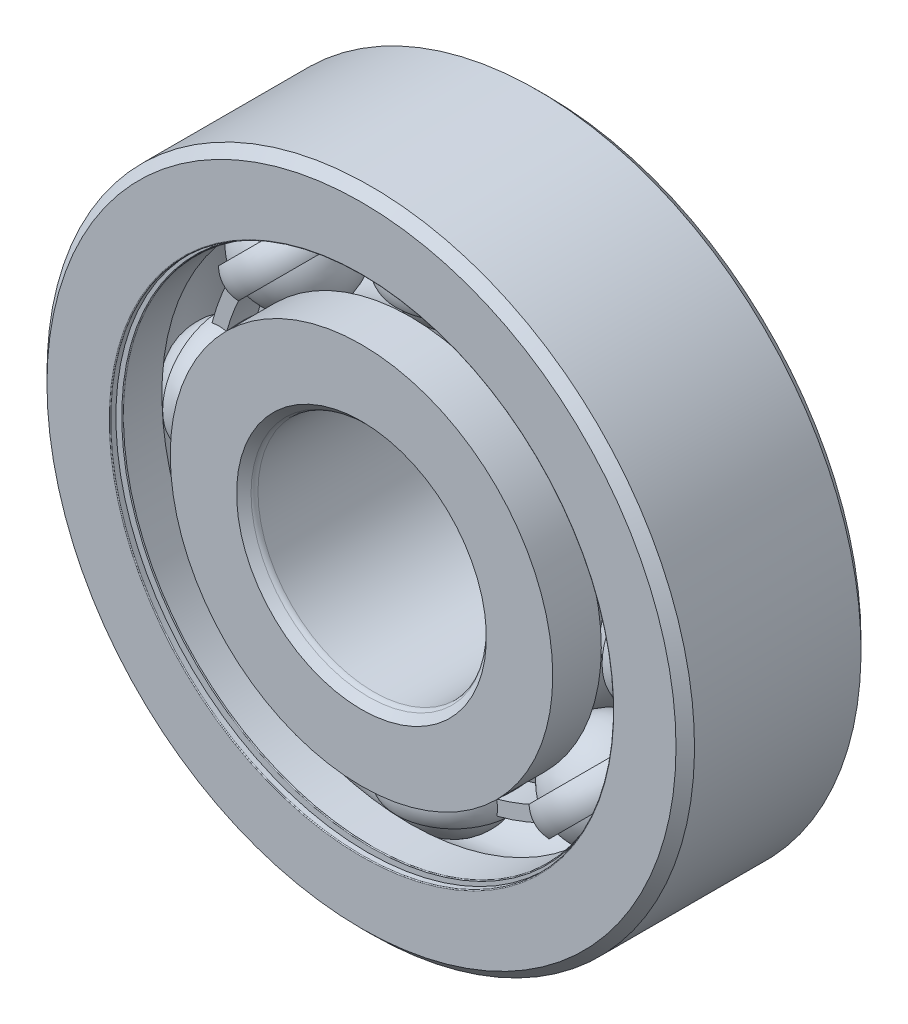
SolidWorks part; units mm, degrees
ref_plane "Front Plane" through (0, 0, 0) normal (0, 0, 1) x (1, 0, 0)
ref_plane "Top Plane" through (0, 0, 0) normal (0, 1, 0) x (1, 0, 0)
ref_plane "Right Plane" through (0, 0, 0) normal (1, 0, 0) x (0, 0, -1)
sketch "Sketch1" plane through (0, 0, 0) normal (0, 0, 1) x (1, 0, 0)
  line L0 (-14, 0) -> (14, 0) construction
  line L1 (-5, 0) -> (5, 0) construction
  circle A0 centre (0, 0) radius 5 construction
  circle A1 centre (0, 0) radius 14 construction
  point P3 (0, 0)
  point P6 (0, 0)
  point P7 (0, -5)
  point P11 (0, -14)
  point P12 (0, 5)
  point P13 (0, 14)
  dimension "OD" = 28
  dimension "ID" = 10
sketch "Sketch2" plane through (0, 0, 0) normal (1, 0, 0) x (0, 0, -1)
  line L0 (-4, 14) -> (4, 14) construction
  line L1 (0, 14) -> (0, -14) construction
  line L2 (3.6, 14) -> (-3.6, 14)
  line L3 (-3.6, 14) -> (-4, 13.6)
  line L4 (-4, 13.6) -> (-4, 10.7308)
  line L5 (-4, 10.7308) -> (-1.9, 10.7308)
  line L6 (4, 10.7308) -> (1.9, 10.7308)
  line L7 (4, 13.6) -> (4, 10.7308)
  line L8 (3.6, 14) -> (4, 13.6)
  line L9 (0, 14) -> (0, 9.5) construction
  line L10 (0, 9.5) -> (0, 5) construction
  line L11 (0, 14) -> (0, -14) construction
  line L12 (-4, 0) -> (4, 0) construction
  line L13 (4, 5) -> (-4, 5) construction
  line L14 (0, 11.7638) -> (0, 7.2362) construction
  line L15 (-4, -5) -> (4, -5) construction
  line L16 (-4, -5) -> (-4, 5) construction
  line L17 (4, 14) -> (4, -14) construction
  arc A0 (-1.9, 10.7308) -> (1.9, 10.7308) centre (0, 9.5) cw
  circle A1 centre (0, 9.5) radius 2.2638 construction
  point P14 (0, 5)
  point P17 (0, 0)
  point P21 (0, 14)
  point P29 (0, 5)
  point P30 (0, -5)
  point P35 (0, 11.7638)
  dimension "Approx. Ball Dia." = 4.5276
  dimension "Width" = 8
  dimension "D1" = 45
  dimension "D2" = 0.4
  dimension "D3" = 3.8
  dimension "D4" = 1.2308
  dimension "For Shaft Diameter" = 10
  dimension "For Housing ID" = 28
sketch "Sketch3" plane through (0, 0, 0) normal (1, 0, 0) x (0, 0, -1)
  line L0 (3.6, 14) -> (4, 13.6) construction
  line L1 (4, 13.6) -> (4, 10.7308) construction
  line L2 (4, 10.7308) -> (1.9, 10.7308) construction
  line L3 (-4, 10.7308) -> (-1.9, 10.7308) construction
  line L4 (-4, 13.6) -> (-4, 10.7308) construction
  line L5 (-3.6, 14) -> (-4, 13.6) construction
  line L6 (3.6, 14) -> (-3.6, 14) construction
  line L7 (3.6, 14) -> (4, 13.6)
  line L8 (4, 13.6) -> (4, 10.7308)
  line L9 (4, 10.7308) -> (1.9, 10.7308)
  line L10 (-4, 10.7308) -> (-1.9, 10.7308)
  line L11 (-4, 13.6) -> (-4, 10.7308)
  line L12 (-3.6, 14) -> (-4, 13.6)
  line L13 (3.6, 14) -> (-3.6, 14)
  arc A0 (1.9, 10.7308) -> (-1.9, 10.7308) centre (0, 9.5) ccw construction
  arc A1 (1.9, 10.7308) -> (-1.9, 10.7308) centre (0, 9.5) ccw
revolve "Revolve1" add sketch "Sketch3" angle 360 about L12
sketch "Sketch8" plane through (0, 0, 0) normal (1, 0, 0) x (0, 0, -1)
  line L0 (-4, 10.7308) -> (-1.9, 10.7308) construction
  line L1 (-3.744, 10.7308) -> (-3.6, 10.7308)
  line L2 (-3.744, 10.7308) -> (-3.744, 11.8205) construction
  line L3 (-3.744, 11.8205) -> (-3.6, 11.8205)
  line L4 (-3.6, 10.7308) -> (-3.6, 11.8205)
  line L5 (4, 10.7308) -> (1.9, 10.7308) construction
  line L6 (3.6, 10.7308) -> (3.744, 10.7308)
  line L7 (3.6, 10.7308) -> (3.6, 11.8205)
  line L8 (3.6, 11.8205) -> (3.744, 11.8205)
  line L9 (3.744, 10.7308) -> (3.744, 11.8205) construction
  line L10 (-3.6, 11.8205) -> (3.6, 11.8205) construction
  line L11 (0, 14) -> (0, -14) construction
  line L12 (-3.744, 11.8205) -> (-3.744, 12.9103) construction
  line L13 (-3.744, 12.9103) -> (-3.744, 14) construction
  line L14 (-4, 14) -> (4, 14) construction
  line L15 (-3.744, 10.7308) -> (-4, 10.7308)
  line L16 (-4, 10.7308) -> (-4, 10.8748)
  line L17 (-4, 13.6) -> (-4, 10.7308) construction
  line L18 (-4, 10.8748) -> (-3.744, 10.8748)
  line L19 (-3.744, 10.8748) -> (-3.744, 11.8205)
  line L20 (3.744, 10.7308) -> (4, 10.7308)
  line L21 (4, 10.7308) -> (4, 10.8748)
  line L22 (4, 13.6) -> (4, 10.7308) construction
  line L23 (4, 10.8748) -> (3.744, 10.8748)
  line L24 (3.744, 10.8748) -> (3.744, 11.8205)
  point P12 (0, 11.8205)
  dimension "D1" = 7.2
  dimension "D2" = 0.144
revolve "Cut-Revolve1" cut sketch "Sketch8" angle 360 about L12
sketch "Sketch4" plane through (0, 0, 0) normal (1, 0, 0) x (0, 0, -1)
  line L0 (0, 14) -> (0, -14) construction
  line L1 (0, 14) -> (0, -14) construction
  line L2 (-3.6, 5) -> (-4, 5.4)
  line L3 (-4, 5.4) -> (-4, 8.2692)
  line L5 (-4, 8.2692) -> (-1.9, 8.2692)
  line L6 (-3.6, 5) -> (3.6, 5)
  line L8 (3.6, 5) -> (4, 5.4)
  line L10 (4, 5.4) -> (4, 8.2692)
  line L11 (4, 8.2692) -> (1.9, 8.2692)
  line L12 (-4, 13.6) -> (-4, 10.7308) construction
  line L13 (3.6, 14) -> (4, 13.6) construction
  line L15 (4, -13.6) -> (4, 13.6) construction
  line L16 (3.6, 14) -> (3.6, -14) construction
  arc A1 (1.9, 8.2692) -> (-1.9, 8.2692) centre (0, 9.5) cw
  circle A2 centre (0, 9.5) radius 2.2638 construction
  point P1 (0, 5)
revolve "Revolve2" add sketch "Sketch4" angle 360 about L12
sketch "Sketch5" plane through (0, 0, 0) normal (1, 0, 0) x (0, 0, -1)
  line L0 (-2.2638, 9.5) -> (2.2638, 9.5)
  arc A2 (-2.2638, 9.5) -> (2.2638, 9.5) centre (0, 9.5) cw
  arc A3 (1.9, 10.7308) -> (-1.9, 10.7308) centre (0, 9.5) ccw construction
revolve "Revolve3" add sketch "Sketch5" angle 360 about L0
sketch "Sketch6" plane through (0, 0, 0) normal (1, 0, 0) x (0, 0, -1)
  line L0 (-1.9, 10.7308) -> (-1.9, 10.1154) construction
  line L1 (-1.9, 10.1154) -> (-1.9, 9.5) construction
  line L2 (-1.9, 9.5) -> (-1.9, 8.8846) construction
  line L3 (-1.9, 8.8846) -> (-1.9, 8.2692) construction
  line L4 (-4, 10.1154) -> (-3.6964, 10.1154) construction
  line L5 (-1.9, 10.1154) -> (-1.9, 8.8846) construction
  line L7 (-3.6964, 10.1154) -> (-3.3929, 10.1154) construction
  line L8 (-3.3929, 10.1154) -> (-3.0893, 10.1154) construction
  line L10 (0, 14) -> (0, -14) construction
  line L11 (0, 14) -> (0, -14) construction
  line L12 (-4, 10.7308) -> (-4, 10.1154) construction
  line L13 (-2.4821, 10.1154) -> (-2.1786, 10.1154) construction
  line L14 (-4, 13.6) -> (-4, -13.6) construction
  line L15 (-4, 10.1154) -> (-4, 9.5) construction
  line L16 (-4, 9.5) -> (-4, 8.8846) construction
  line L17 (-4, 8.8846) -> (-4, 8.2692) construction
  line L18 (-3.0893, 10.1154) -> (-2.7857, 10.1154) construction
  line L19 (-2.7857, 10.1154) -> (-2.4821, 10.1154) construction
  line L20 (-2.1786, 10.1154) -> (-2.4821, 10.1154)
  line L21 (-4, 8.8846) -> (-3.6964, 8.8846) construction
  line L22 (-3.6964, 8.8846) -> (-3.3929, 8.8846) construction
  line L23 (-3.3929, 8.8846) -> (-3.0893, 8.8846) construction
  line L24 (-3.0893, 8.8846) -> (-2.7857, 8.8846) construction
  line L25 (-2.7857, 8.8846) -> (-2.4821, 8.8846) construction
  line L26 (-2.4821, 8.8846) -> (-2.1786, 8.8846) construction
  line L27 (-2.1786, 8.8846) -> (-2.4821, 8.8846)
  line L28 (-2.7857, 10.1154) -> (-2.7857, 8.8846) construction
  line L30 (-2.6339, 10.1154) -> (-2.6339, 8.8846) construction
  circle A0 centre (0, 9.5) radius 2.2638 construction
  arc A2 (-2.4821, 8.8846) -> (-2.4821, 10.1154) centre (-1.3106, 9.5) cw
  arc A3 (-2.1786, 10.1154) -> (-2.1786, 8.8846) centre (0, 9.5) ccw
revolve "Revolve4" add sketch "Sketch6" angle 360 about L11
sketch "Sketch7" plane through (0, 0, 0) normal (0, 0, 1) x (1, 0, 0)
  line L0 (-2.2638, 9.5) -> (2.2638, 9.5) construction
  line L1 (0, 7.2362) -> (0, 11.7638) construction
  line L2 (0, 0) -> (3.6355, 8.7769) construction
  line L8 (0, 14) -> (0, -14) construction
  line L9 (6.7175, 6.7175) -> (7.1527, 7.1527)
  line L10 (0, 14) -> (0, -14) construction
  line L11 (0, 10.1154) -> (0, 9.5)
  arc A1 (6.7175, 6.7175) -> (0, 9.5) centre (0, 0) ccw
  arc A2 (7.1527, 7.1527) -> (0, 10.1154) centre (0, 0) ccw
  dimension "D1" = 45
  dimension "D2" = 4.5276
extrude "Boss-Extrude1" add sketch "Sketch7" along normal mid plane 1.3333
pattern_circular "CirPattern1" count 8 over 360 about axis through (0, 0, 4) along (0, 0, -1) of bodies 104 134
pattern_circular "CirPattern2" count 8 over 360 about axis through (0, 0, 4) along (0, 0, -1) of "Revolve4", "Boss-Extrude1" reverse direction yes
fillet "Fillet1" radius 0.036 4 edges at (0, -10.7308, -3.6) (0, -10.8748, -4) (0, -10.7308, 3.6) (0, -10.8748, 4)
fillet "Fillet2" radius 0.3 2 edges at (0, -5, -3.6) (0, -5, 3.6)
ref_plane "Plane1" through (3.6355, 8.7769, 0) normal (0.3827, 0.9239, 0) x (0.9239, -0.3827, 0)
sketch "Sketch9" plane through (3.6355, 8.7769, 0) normal (0.3827, 0.9239, 0) x (0.9239, -0.3827, 0)
  line L0 (-1.544, -0.6667) -> (-1.544, -2)
  line L1 (-1.544, -2) -> (-0.6697, -2)
  line L2 (-0.6697, -2) -> (0, -1.438)
  line L3 (0, -1.438) -> (0.6697, -2)
  line L4 (0.6697, -2) -> (1.544, -2)
  line L5 (1.544, -2) -> (1.544, -0.6667)
  line L6 (1.544, -0.6667) -> (-1.544, -0.6667)
  line L7 (0, -0.6667) -> (0, 0) construction
  line L8 (-1.544, -0.6667) -> (-1.544, 0) construction
  dimension "D1" = 1.3333
  dimension "D2" = 0.6667
  dimension "D3" = 40
extrude "Boss-Extrude2" [suppressed] add sketch "Sketch9" along normal blind 1.9808 draft 15 and the other way blind 1.9808 draft 10 separate body draft outward yes other way draft outward yes
fillet "Fillet3" [suppressed] radius 0.4
mirror "Mirror1" [suppressed] about plane through (0, 0, 0) normal (0, 0, 1) of bodies 149
pattern_circular "CirPattern3" [suppressed] count 8 over 360 about axis through (0, 0, 4) along (0, 0, -1) of bodies 158 149
equation "\"D2@Sketch2\" = \"Width@Sketch2\" * .05"
equation "\"D3@Sketch2\"=\"Width@Sketch2\" * .475"
equation "\"D4@Sketch2\" =  (  (  ( \"OD@Sketch1\" - \"Width@Sketch2\" )  / 2 )  / 3.25 )  / 2.5"
equation "\"D1@Boss-Extrude1\" = \"Width@Sketch2\" / 6"
equation "\"D1@Sketch8\"=\"Width@Sketch2\"*.9"
equation "\"D2@Sketch8\"=\"D1@Sketch8\"*.02"
equation "\"D1@Fillet1\" = \"D2@Sketch8\" * .25"
equation "\"D1@Fillet2\" = \"D2@Sketch2\" * .75"
equation "\"Approx No of Balls@CirPattern1\" = ( pi * \"OD@Sketch1\" ) * .4 / \"Approx. Ball Dia.@Sketch2\""
equation "\"D1@Sketch7\" = 360 / \"Approx No of Balls@CirPattern1\""
equation "\"D1@CirPattern2\" = \"Approx No of Balls@CirPattern1\""
equation "\"D2@Sketch7\"=\"Approx. Ball Dia.@Sketch2\""
equation "\"D2@Sketch9\" = \"D1@Boss-Extrude1\" * .5"
equation "\"D1@Sketch9\"=\"D2@Sketch9\"*2"
equation "\"D1@Boss-Extrude2\"=\"Approx. Ball Dia.@Sketch2\"*.4375"
equation "\"D2@Boss-Extrude2\"=\"D1@Boss-Extrude2\""
equation "\"D1@CirPattern3\" = \"Approx No of Balls@CirPattern1\""
equation "\"D1@Fillet3\"=\"D1@Sketch9\" * .3"
